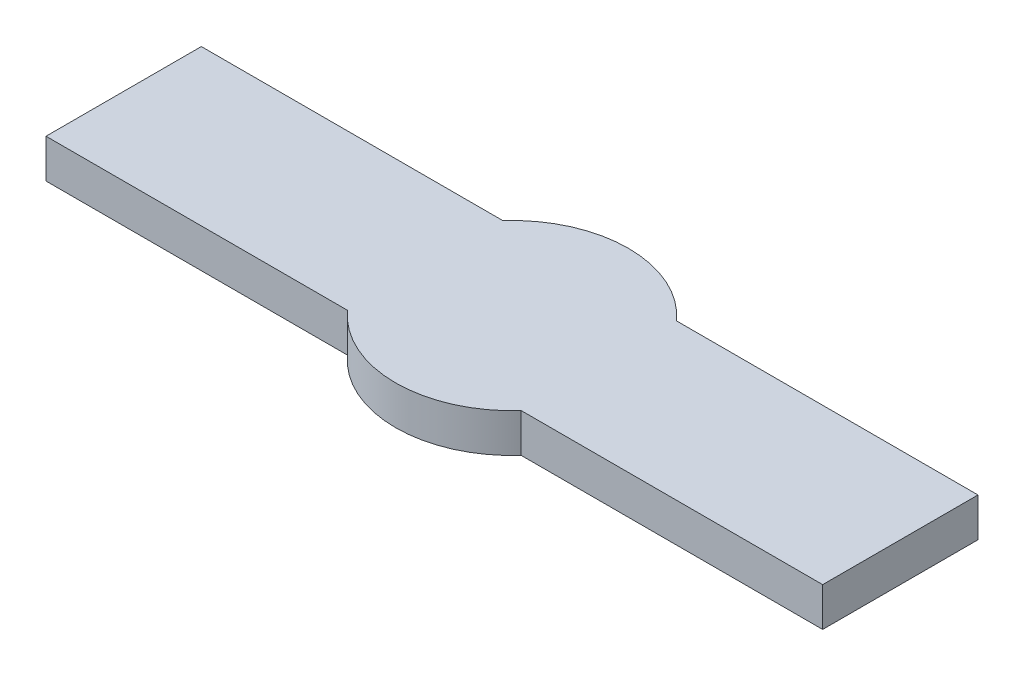
SolidWorks part; units mm, degrees
material "AR500 Steel"
ref_plane "Front" through (0, 0, 0) normal (0, 0, 1) x (1, 0, 0)
ref_plane "Top" through (0, 0, 0) normal (0, 1, 0) x (1, 0, 0)
ref_plane "Right" through (0, 0, 0) normal (1, 0, 0) x (0, 0, -1)
sketch "Sketch1" plane through (0, 0, 0) normal (0, 1, 0) x (1, 0, 0)
  line L1 (-127, 25.4) -> (127, 25.4)
  line L2 (-127, 25.4) -> (-127, -25.4)
  line L3 (-127, -25.4) -> (127, -25.4)
  line L4 (127, 25.4) -> (127, -25.4)
  line L5 (-127, 25.4) -> (127, -25.4) construction
  line L6 (-127, -25.4) -> (127, 25.4) construction
  circle A0 centre (0, 0) radius 38.1
  dimension "D1" = 76.2
  dimension "D2" = 254
  dimension "D3" = 50.8
extrude "Boss-Extrude1" add sketch "Sketch1" along normal blind 12.7 contours L3 A0 L1 | A0 L1 L2 L3 | L1 A0 | L3 A0 | A0 L3 L4 L1 region at (-80.9821, 0, 0) region at (0, 0, -30.5604) region at (0, 0, 0) region at (80.9821, 0, 0) region at (0, 0, 30.5604)
